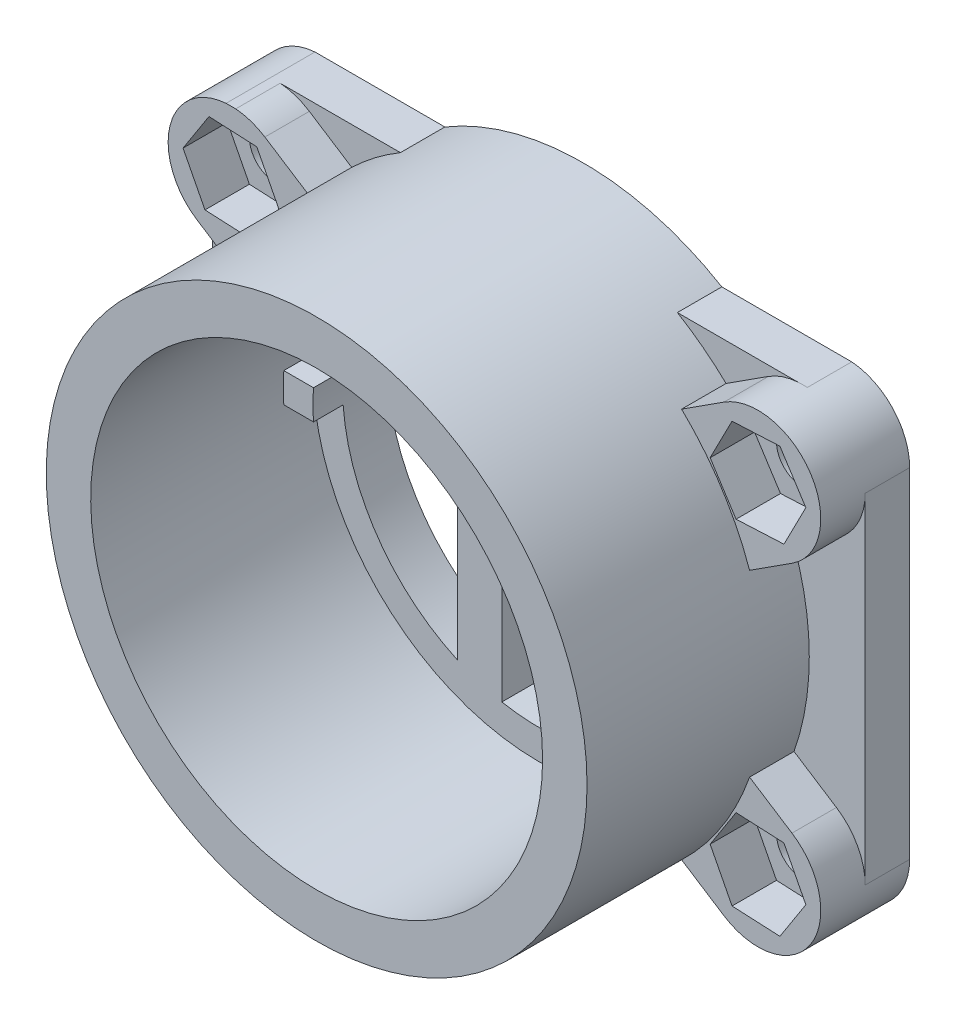
SolidWorks part; units mm, degrees
ref_plane "Front Plane" through (0, 0, 0) normal (0, 0, 1) x (1, 0, 0)
ref_plane "Top Plane" through (0, 0, 0) normal (0, 1, 0) x (1, 0, 0)
ref_plane "Right Plane" through (0, 0, 0) normal (1, 0, 0) x (0, 0, -1)
sketch "Sketch1" plane through (0, 0, 0) normal (0, 0, 1) x (1, 0, 0)
  line L4 (18.1127, 15.675) -> (-18.1127, 15.675)
  line L5 (-22.025, 11.45) -> (-22.025, -11.45)
  line L6 (-18.1127, -15.675) -> (18.1127, -15.675)
  line L7 (22.025, -11.45) -> (22.025, 11.45)
  line L8 (18.1127, 15.675) -> (-18.1127, 15.675)
  line L9 (-22.025, 11.45) -> (-22.025, -11.45)
  line L10 (-18.1127, -15.675) -> (18.1127, -15.675)
  line L11 (22.025, -11.45) -> (22.025, 11.45)
  circle A0 centre (-17.7875, -11.45) radius 1.75 construction
  circle A1 centre (-17.7875, 11.45) radius 1.75 construction
  circle A2 centre (17.7875, 11.45) radius 1.75 construction
  circle A3 centre (17.7875, -11.45) radius 1.75 construction
  arc A4 (-18.1127, 15.675) -> (-22.025, 11.45) centre (-17.7875, 11.45) ccw
  arc A5 (-22.025, -11.45) -> (-18.1127, -15.675) centre (-17.7875, -11.45) ccw
  arc A6 (18.1127, -15.675) -> (22.025, -11.45) centre (17.7875, -11.45) ccw
  arc A7 (22.025, 11.45) -> (18.1127, 15.675) centre (17.7875, 11.45) ccw
  arc A8 (-18.1127, 15.675) -> (-22.025, 11.45) centre (-17.7875, 11.45) ccw
  arc A9 (-22.025, -11.45) -> (-18.1127, -15.675) centre (-17.7875, -11.45) ccw
  arc A10 (18.1127, -15.675) -> (22.025, -11.45) centre (17.7875, -11.45) ccw
  arc A11 (22.025, 11.45) -> (18.1127, 15.675) centre (17.7875, 11.45) ccw
  circle A12 centre (-17.7875, -11.45) radius 1.75
  circle A13 centre (-17.7875, 11.45) radius 1.75
  circle A14 centre (17.7875, 11.45) radius 1.75
  circle A15 centre (17.7875, -11.45) radius 1.75
  circle A16 centre (0, 0) radius 15.25
  circle A17 centre (0, 0) radius 18.25
  circle A18 centre (0, 0) radius 13.25
  dimension "D2" = 30.5
  dimension "D3" = 3
  dimension "D4" = 26.5
  dimension "D1" = 0
extrude "Boss-Extrude1" add sketch "Sketch1" along normal blind 3 contours A17 L8 A8 L9 A9 L10 A12 A13 | L8 A17 L10 A16 | L8 A17 | L10 A17 | A16 | A17 L10 A10 L11 A11 L8 A15 A14 region at (18.2872, 0, 0) region at (15.4504, 8.7759, 0) region at (0, 16.7115, 0) region at (-18.2872, 0, 0) region at (0, -16.7115, 0) region at (-14.8187, 0, 0)
sketch "Sketch3" plane through (0, 0, 3) normal (0, 0, 1) x (1, 0, 0)
  circle A0 centre (0, 0) radius 18.25
  arc A1 (9.3465, 15.675) -> (-9.3465, 15.675) centre (0, 0) ccw construction
  circle A2 centre (0, 0) radius 15.25
  dimension "D1" = 30.5
extrude "Boss-Extrude2" add sketch "Sketch3" along normal blind 15
sketch "Sketch4" plane through (0, 0, 3) normal (0, 0, 1) x (1, 0, 0)
  line L0 (-15.4939, 15.0131) -> (-12.6325, 13.1712)
  line L1 (-17.7875, 11.45) -> (0, 0) construction
  line L2 (-20.0811, 7.8869) -> (-17.2198, 6.045)
  line L3 (0, 18.25) -> (0, -18.25) construction
  line L4 (-18.25, 0) -> (18.25, 0) construction
  line L5 (15.4939, 15.0131) -> (12.6325, 13.1712)
  line L6 (20.0811, 7.8869) -> (17.2198, 6.045)
  line L7 (20.0811, -7.8869) -> (17.2198, -6.045)
  line L8 (15.4939, -15.0131) -> (12.6325, -13.1712)
  line L9 (-15.4939, -15.0131) -> (-12.6325, -13.1712)
  line L10 (-20.0811, -7.8869) -> (-17.2198, -6.045)
  line L11 (19.5375, 8.7314) -> (16.3081, 8.5752)
  line L12 (-19.2669, 14.3248) -> (-21.0169, 11.6062)
  line L13 (-21.0169, 11.6062) -> (-19.5375, 8.7314)
  line L14 (-19.5375, 8.7314) -> (-16.3081, 8.5752)
  line L15 (-16.3081, 8.5752) -> (-14.5581, 11.2938)
  line L16 (-14.5581, 11.2938) -> (-16.0375, 14.1686)
  line L17 (-16.0375, 14.1686) -> (-19.2669, 14.3248)
  line L18 (16.3081, 8.5752) -> (14.5581, 11.2938)
  line L19 (14.5581, 11.2938) -> (16.0375, 14.1686)
  line L20 (16.0375, 14.1686) -> (19.2669, 14.3248)
  line L21 (19.2669, 14.3248) -> (21.0169, 11.6062)
  line L22 (21.0169, 11.6062) -> (19.5375, 8.7314)
  line L23 (-14.5581, -11.2938) -> (-16.0375, -14.1686)
  line L24 (-16.3081, -8.5752) -> (-14.5581, -11.2938)
  line L25 (-19.5375, -8.7314) -> (-16.3081, -8.5752)
  line L26 (-21.0169, -11.6062) -> (-19.5375, -8.7314)
  line L27 (-19.2669, -14.3248) -> (-21.0169, -11.6062)
  line L28 (-16.0375, -14.1686) -> (-19.2669, -14.3248)
  line L29 (16.3081, -8.5752) -> (14.5581, -11.2938)
  line L30 (19.5375, -8.7314) -> (16.3081, -8.5752)
  line L31 (21.0169, -11.6062) -> (19.5375, -8.7314)
  line L32 (19.2669, -14.3248) -> (21.0169, -11.6062)
  line L33 (16.0375, -14.1686) -> (19.2669, -14.3248)
  line L34 (14.5581, -11.2938) -> (16.0375, -14.1686)
  circle A0 centre (-17.7875, 11.45) radius 4.2375
  arc A1 (-18.1127, 15.675) -> (-22.025, 11.45) centre (-17.7875, 11.45) ccw construction
  arc A2 (-9.3465, 15.675) -> (-9.3465, -15.675) centre (0, 0) ccw construction
  circle A3 centre (0, 0) radius 18.25 construction
  circle A4 centre (0, 0) radius 18.25
  circle A5 centre (17.7875, 11.45) radius 4.2375
  circle A6 centre (17.7875, -11.45) radius 4.2375
  circle A7 centre (-17.7875, -11.45) radius 4.2375
  circle A8 centre (-17.7875, 11.45) radius 2.8 construction
  arc M19 (-9.3465, -15.675) -> (-9.3465, 15.675) centre (0, 0) cw
  line M20 (-9.3465, 15.675) -> (-18.1127, 15.675)
  arc M21 (-18.1127, 15.675) -> (-22.025, 11.45) centre (-17.7875, 11.45) ccw
  arc M23 (-22.025, -11.45) -> (-18.1127, -15.675) centre (-17.7875, -11.45) ccw
  line M24 (-18.1127, -15.675) -> (-9.3465, -15.675)
  dimension "D1" = 5.6
extrude "Boss-Extrude3" add sketch "Sketch4" along normal blind 3 contours A0 L17 L16 L15 L14 L13 L12 M19 M20 M21 | A0 L0 M19 | A0 L2 M19 | A4 A5 L5 | A5 A4 L21 L22 L11 L18 L19 L20 | L6 A5 A4 | A6 L7 A4 | A6 A4 L34 L29 L30 L31 L32 L33 | A6 A4 L8 | A7 L9 M19 | A7 A4 L23 L28 L27 L26 L25 L24 M23 M24 | L10 A7 M19 region at (-13.6332, 13.3344, 3) region at (-14.3507, 13.7188, 3) region at (-17.7826, 6.8883, 3) region at (13.6332, 13.3344, 3) region at (19.7597, 15.0651, 3) region at (-17.7826, -6.8883, 3) region at (17.7826, 6.8883, 3) region at (-18.4296, -7.3822, 3) region at (-13.6332, -13.3344, 3) region at (17.7826, -6.8883, 3) region at (21.4026, -9.4778, 3) region at (13.6332, -13.3344, 3)
sketch "Sketch5" plane through (0, 0, 3) normal (0, 0, 1) x (1, 0, 0)
  line L1 (-15.25, -1) -> (15.25, -1)
  line L2 (-15.25, -1) -> (-15.25, 1)
  line L3 (-15.25, 1) -> (15.25, 1)
  line L4 (15.25, -1) -> (15.25, 1)
  line L5 (-15.25, -1) -> (15.25, 1) construction
  line L6 (-15.25, 1) -> (15.25, -1) construction
  circle A0 centre (0, 0) radius 15.25 construction
  circle A1 centre (0, 0) radius 13.25 construction
  circle A2 centre (0, 0) radius 13.25
  point P0 (0, 0)
  circle M3 centre (0, 0) radius 13.25
  circle M4 centre (0, 0) radius 15.25
  dimension "D1" = 2
extrude "Boss-Extrude4" add sketch "Sketch5" along normal blind 2 contours L3 L1 M4 M3 | L3 L1 M3 M4 region at (-14.2382, 0, 3) region at (14.2382, 0, 3)
sketch "Sketch6" plane through (0, 0, 0) normal (0, 0, -1) x (-1, 0, 0)
  line L0 (0, 13.25) -> (0, -13.25) construction
  line L1 (-4, 12.6318) -> (-4, -12.6318) construction
  line L2 (5.5, -13.012) -> (2.5, -13.012)
  line L3 (-5.5, -13.012) -> (-2.5, -13.012)
  line L4 (-5.5, -13.012) -> (-5.5, 13.012)
  line L5 (-5.5, 13.012) -> (-2.5, 13.012)
  line L6 (-2.5, -13.012) -> (-2.5, 13.012)
  line L7 (-5.5, -13.012) -> (-2.5, 13.012) construction
  line L8 (-5.5, 13.012) -> (-2.5, -13.012) construction
  line L9 (2.5, -13.012) -> (2.5, 13.012)
  line L10 (5.5, 13.012) -> (2.5, 13.012)
  line L11 (5.5, -13.012) -> (5.5, 13.012)
  circle A0 centre (0, 0) radius 13.25 construction
  circle A1 centre (0, 0) radius 13.25
  point P7 (-4, 0)
  circle M24 centre (0, 0) radius 13.25
  dimension "D1" = 4
  dimension "D2" = 3
extrude "Boss-Extrude5" add sketch "Sketch6" against normal up to surface (3 mm away) contours L6 L4 M24 | L11 L9 M24 region at (-3.9811, 0, 0) region at (3.9811, 0, 0) up to face at (0, 7.625, 3)
